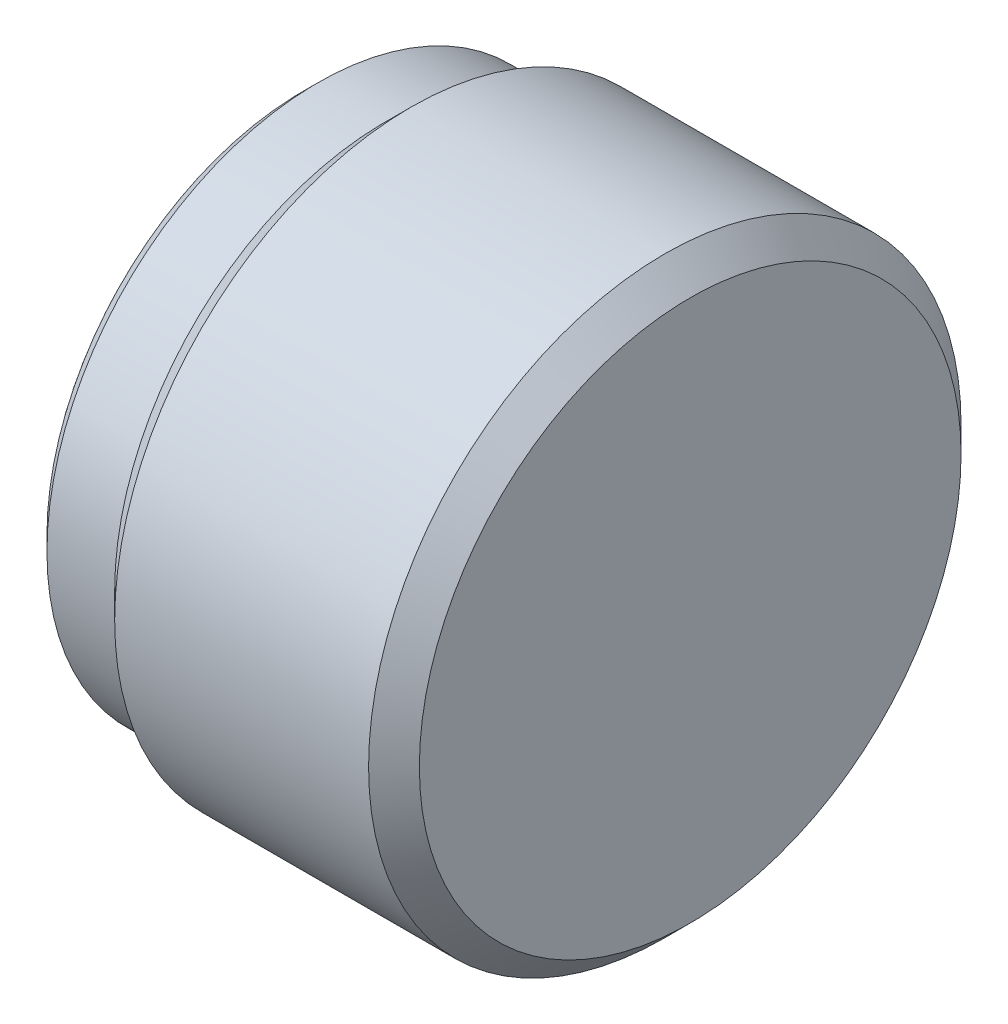
SolidWorks part; units mm, degrees
ref_plane "Спереди" through (0, 0, 0) normal (0, 0, 1) x (1, 0, 0)
ref_plane "Сверху" through (0, 0, 0) normal (0, 1, 0) x (1, 0, 0)
ref_plane "Справа" through (0, 0, 0) normal (1, 0, 0) x (0, 0, -1)
sketch "Эскиз1" plane through (0, 0, 0) normal (0, 1, 0) x (1, 0, 0)
  line L0 (0, 0) -> (104.9, 0) construction
  line L1 (24.3, 16) -> (25.8, 17.5)
  line L2 (0, 0) -> (16.3, 0)
  line L3 (0, 0) -> (0, 3)
  line L4 (0, 3) -> (16.3, 3)
  line L5 (16.3, 0) -> (16.3, 3)
  line L6 (16.3, 0) -> (19.3, 0)
  line L7 (16.3, 0) -> (16.3, 10)
  line L8 (16.3, 10) -> (19.3, 10)
  line L9 (19.3, 0) -> (19.3, 10)
  line L10 (19.3, 0) -> (24.3, 0)
  line L11 (19.3, 0) -> (19.3, 15)
  line L12 (20.3, 16) -> (24.3, 16)
  line L13 (24.3, 0) -> (24.3, 16)
  line L14 (24.3, 0) -> (42.3, 0)
  line L15 (24.3, 0) -> (24.3, 16)
  line L16 (25.8, 17.5) -> (40.8, 17.5)
  line L17 (42.3, 0) -> (42.3, 16)
  line L18 (19.3, 15) -> (20.3, 16)
  line L19 (40.8, 17.5) -> (42.3, 16)
  line L21 (42.3, 0) -> (47.3, 0)
  line L22 (42.3, 0) -> (42.3, 16)
  line L23 (42.3, 16) -> (47.3, 16)
  line L24 (47.3, 0) -> (47.3, 16)
  line L25 (47.3, 0) -> (104.3, 0)
  line L26 (47.3, 0) -> (47.3, 16)
  line L27 (49.3, 18) -> (104.3, 18)
  line L28 (104.3, 0) -> (104.3, 18)
  arc A0 (47.3, 16) -> (49.3, 18) centre (49.3, 16) cw
  point P10 (19.3, 16)
  point P12 (42.3, 17.5)
  point P13 (24.3, 17.5)
  point P28 (47.3, 18)
  dimension "D14" = 2
  dimension "D2" = 3
  dimension "D3" = 16.3
  dimension "D4" = 3
  dimension "D5" = 10
  dimension "D6" = 16
  dimension "D7" = 5
  dimension "D8" = 17.5
  dimension "D9" = 18
  dimension "D10" = 5
  dimension "D11" = 18
  dimension "D12" = 57
  dimension "D15" = 104.3
  dimension "D16" = 31
  dimension "D17" = 88
revolve "Повернуть1 основной корпус" add sketch "Эскиз1" angle 360 about L0 region at (21.8136, 0, -7.9518) region at (33.3, 0, -8.6906) region at (17.8, 0, -5) region at (44.8, 0, -8) region at (8.15, 0, -1.5) region at (75.8235, 0, -8.9928)
sketch "Эскиз19" plane through (0, 0, 0) normal (0, 1, 0) x (1, 0, 0)
  line L0 (103.0047, 0) -> (0, 0) construction
  line L1 (104.3, 18) -> (101.3, 18)
  line L2 (104.3, 18) -> (104.3, 17.95)
  line L3 (104.3, 17.95) -> (101.3, 17.95)
  line L4 (101.3, 18) -> (101.3, 17.95)
  dimension "D1" = 3
  dimension "D2" = 0.05
revolve "Вырез-Повернуть2 пластиковая часть" cut sketch "Эскиз19" angle 360 about L0
sketch "Эскиз20" plane through (104.3, 0, 0) normal (1, 0, 0) x (0, 0, -1)
  circle A0 centre (0, 0) radius 18
  dimension "D1" = 36
extrude "Бобышка-Вытянуть2 пластиковая крышка контактов" add sketch "Эскиз20" along normal blind 14
sketch "Эскиз11" plane through (16.3, 0, 0) normal (-1, 0, 0) x (0, 0, 1)
  line L0 (-4.3589, 9) -> (4.3589, 9)
  line L1 (4.3589, -9) -> (-4.3589, -9)
  circle A0 centre (0, 0) radius 10 construction
  circle A3 centre (0, 0) radius 10
  circle M1 centre (0, 0) radius 10
  dimension "D1" = 18
  dimension "D2" = 9
extrude "Вырез-Вытянуть6" cut sketch "Эскиз11" against normal blind 3 contours L0 M1 | L1 M1 region at (16.3, 9.4018, 0) region at (16.3, -9.4018, 0)
sketch "Эскиз6" plane through (0, 0, 0) normal (-1, 0, 0) x (0, 0, 1)
  line L0 (1.5611, 2.5618) -> (-1.7531, 2.4345)
  circle A0 centre (0, 0) radius 3
  circle M1 centre (0, 0) radius 3
  dimension "D2" = 6
  dimension "D1" = 2.5
extrude "Вырез-Вытянуть4 на оси" cut sketch "Эскиз6" against normal blind 12 contours L0 M1 region at (0, 2.6995, -0.1037)
sketch "Эскиз13" plane through (19.3, 0, 0) normal (-1, 0, 0) x (0, 0, 1)
  line L0 (0, 0) -> (-9.1924, 9.1924)
  circle A0 centre (0, 0) radius 13
  circle A2 centre (-9.1924, 9.1924) radius 1.5
  dimension "D1" = 26
  dimension "D2" = 3
extrude "Вырез-Вытянуть8 для винтов" cut sketch "Эскиз13" against normal blind 7 contours A0 A2 | L0 A2 A0 | A0 A2 L0 region at (19.3, 8.2899, -9.1729) region at (19.3, 9.1729, -8.2899) region at (19.3, 9.6313, -9.6313)
pattern_circular "Круговой массив2 для винтов" count 4 every 90 about axis through (0, 0, 0) along (-1, 0, 0) of face at (26.3, 9.1924, -7.6924) of face at (26.3, 9.1924, -7.6924)
fillet "Скругление1" radius 0.5 16 edges at (19.3, 0, 10) (19.3, 0, -10) (19.3, 0, 15) (19.3, 9.1924, -7.6924) (19.3, -7.6924, -9.1924) (19.3, -9.1924, 7.6924) (19.3, 7.6924, 9.1924) (17.8, 9, -4.3589) (19.3, 9, 0) (17.8, 9, 4.3589) (16.3, 9, 0) (17.8, -9, 4.3589) (19.3, -9, 0) (17.8, -9, -4.3589) (16.3, -9, 0) (118.3, 0, -18)
sketch "Эскиз21" plane through (118.3, 0, 0) normal (1, 0, 0) x (0, 0, -1)
  circle A0 centre (0, 0) radius 20
  dimension "D1" = 40
extrude "Вырез-Вытянуть7" cut sketch "Эскиз21" against normal blind 76
sketch "Эскиз23" plane through (0, 0, 0) normal (-1, 0, 0) x (0, 0, 1)
  circle A0 centre (0, 0) radius 3
  arc A1 (-1.7531, 2.4345) -> (1.5611, 2.5618) centre (0, 0) ccw construction
extrude "Вырез-Вытянуть8" cut sketch "Эскиз23" against normal blind 16.3
